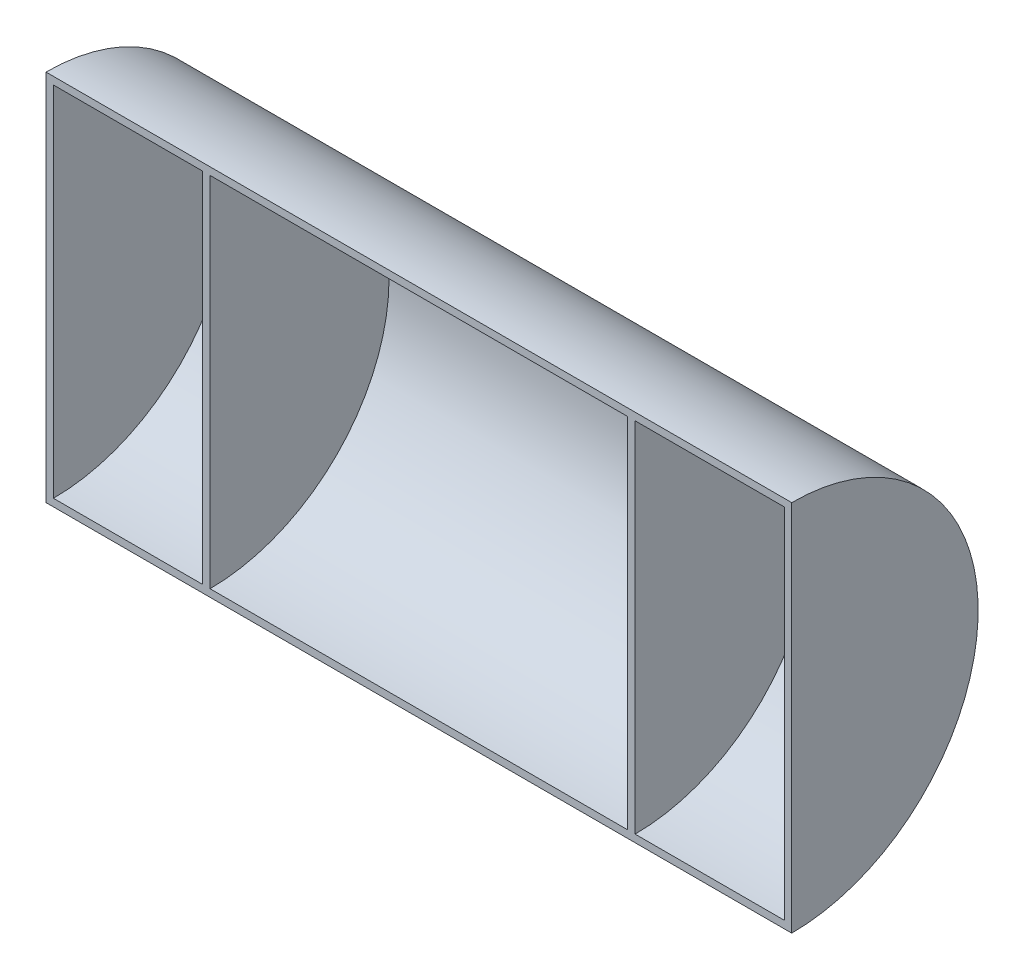
SolidWorks part; units mm, degrees
ref_plane "Front Plane" through (0, 0, 0) normal (0, 0, 1) x (1, 0, 0)
ref_plane "Top Plane" through (0, 0, 0) normal (0, 1, 0) x (1, 0, 0)
ref_plane "Right Plane" through (0, 0, 0) normal (1, 0, 0) x (0, 0, -1)
sketch "Profile Sketch" plane through (0, 0, 0) normal (1, 0, 0) x (0, 0, -1)
  line L0 (0, 50) -> (0, -50)
  arc A0 (0, -50) -> (0, 50) centre (0, 0) ccw
  dimension "D1" = 100
extrude "Profile Extrude" add sketch "Profile Sketch" against normal blind 200
shell "Profile Shell" thickness 2 removed face at (-100, 0, 0)
sketch "Support Sketch" plane through (0, 0, 0) normal (0, 0, 1) x (1, 0, 0)
  line L0 (-198, 48) -> (-2, 48) construction
  line L1 (-198, -48) -> (-2, -48) construction
  line L2 (-158, 48) -> (-156, 48)
  line L3 (-158, 48) -> (-158, -48)
  line L4 (-158, -48) -> (-156, -48)
  line L5 (-156, 48) -> (-156, -48)
  line L6 (-158, 48) -> (-156, -48) construction
  line L7 (-158, -48) -> (-156, 48) construction
  line L8 (-198, -48) -> (-198, 48) construction
  line L9 (-44, 48) -> (-42, 48)
  line L10 (-44, 48) -> (-44, -48)
  line L11 (-44, -48) -> (-42, -48)
  line L12 (-42, 48) -> (-42, -48)
  line L13 (-44, 48) -> (-42, -48) construction
  line L14 (-44, -48) -> (-42, 48) construction
  line L15 (-2, 48) -> (-2, -48) construction
  point P1 (-157, 0)
  point P7 (-43, 0)
  dimension "D1" = 2
  dimension "D2" = 2
  dimension "D3" = 40
  dimension "D4" = 40
extrude "Support Extrude" add sketch "Support Sketch" against normal up to surface up to face at (-100, 0, -24)
sketch "Angle Sketch" plane through (0, 0, 0) normal (1, 0, 0) x (0, 0, -1)
  line L0 (0, 0) -> (50, 0) construction
  arc A0 (0, -50) -> (0, 50) centre (0, 0) ccw construction
  point P7 (50, 0)
